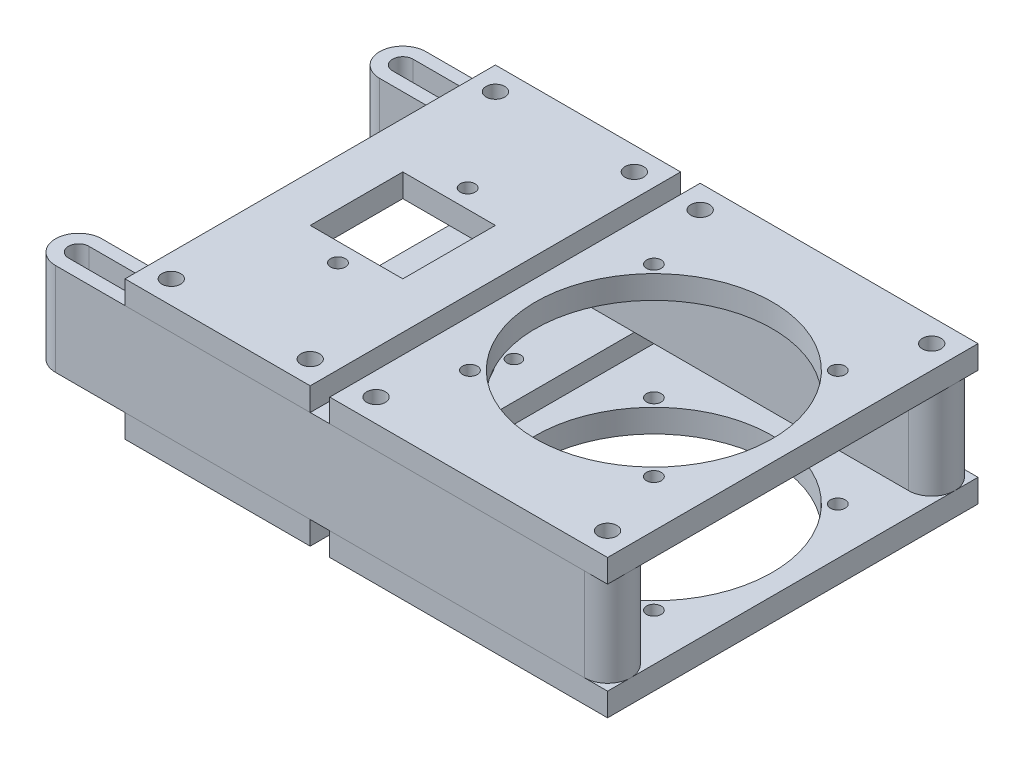
SolidWorks part; units mm, degrees
material "Alum Plate"
ref_plane "Front Plane" through (0, 0, 0) normal (0, 0, 1) x (1, 0, 0)
ref_plane "Top Plane" through (0, 0, 0) normal (0, 1, 0) x (1, 0, 0)
ref_plane "Right Plane" through (0, 0, 0) normal (1, 0, 0) x (0, 0, -1)
sketch "Sketch2" plane through (0, 0, 0) normal (0, 1, 0) x (1, 0, 0)
  line L0 (0, 0) -> (-68.8619, 0) construction
  line L1 (-38.1, -50.8) -> (-38.1, 50.8)
  line L2 (-38.1, 50.8) -> (38.1, 50.8)
  line L4 (-38.1, -50.8) -> (38.1, -50.8)
  line L5 (38.1, 50.8) -> (38.1, -50.8)
  line L7 (-94.2619, 50.8) -> (-43.4619, 50.8)
  line L8 (-81.5619, 12.7) -> (-56.1619, 12.7) construction
  line L9 (-81.5619, 12.7) -> (-81.5619, -12.7) construction
  line L10 (-81.5619, -12.7) -> (-56.1619, -12.7) construction
  line L11 (-56.1619, 12.7) -> (-56.1619, -12.7) construction
  line L12 (-81.5619, 12.7) -> (-56.1619, -12.7) construction
  line L13 (-81.5619, -12.7) -> (-56.1619, 12.7) construction
  line L14 (-38.1, -50.8) -> (38.1, 50.8) construction
  line L15 (-94.2619, 50.8) -> (-94.2619, -50.8)
  line L16 (-94.2619, -50.8) -> (-43.4619, -50.8)
  line L17 (-43.4619, 50.8) -> (-43.4619, -50.8)
  line L18 (-94.2619, 50.8) -> (-43.4619, -50.8) construction
  line L19 (-94.2619, -50.8) -> (-43.4619, 50.8) construction
  circle A0 centre (0, 0) radius 32.5
  circle A1 centre (-68.8619, 0) radius 18 construction
  point P5 (-34.431, 0)
  point P8 (-38.1, 0)
  dimension "D1" = 65
  dimension "D2" = 36
  dimension "D3" = 68.8619
  dimension "D4" = 38.1
  dimension "D5" = 50.8
  dimension "D6" = 25.4
  dimension "D7" = 25.4
  dimension "D8" = 50.8
extrude "Boss-Extrude1" add sketch "Sketch2" against normal blind 6.35 from offset 19.05
mirror "Mirror1" about plane through (0, 0, 0) normal (0, 1, 0) of bodies 101 109
sketch "Sketch3" plane through (0, 19.05, 0) normal (0, 1, 0) x (1, 0, 0)
  line L1 (-81.5619, -12.7) -> (-56.1619, -12.7)
  line L2 (-81.5619, -12.7) -> (-81.5619, 12.7)
  line L3 (-81.5619, 12.7) -> (-56.1619, 12.7)
  line L4 (-56.1619, -12.7) -> (-56.1619, 12.7)
  line L5 (-81.5619, -12.7) -> (-56.1619, 12.7) construction
  line L6 (-81.5619, 12.7) -> (-56.1619, -12.7) construction
  point P4 (-68.8619, 0)
extrude "Cut-Extrude1" cut sketch "Sketch3" against normal up to next (6.35 mm away)
sketch "Sketch4" plane through (0, -19.05, 0) normal (0, -1, 0) x (1, 0, 0)
  circle A0 centre (-68.8619, 0) radius 18 construction
  circle A1 centre (-68.8619, 0) radius 18
extrude "Cut-Extrude2" cut sketch "Sketch4" against normal up to next (6.35 mm away)
sketch "Sketch5" plane through (0, -19.05, 0) normal (0, -1, 0) x (1, 0, 0)
  line L1 (-84.1019, 15.24) -> (-53.6219, 15.24) construction
  line L2 (-84.1019, 15.24) -> (-84.1019, -15.24) construction
  line L3 (-84.1019, -15.24) -> (-53.6219, -15.24) construction
  line L4 (-53.6219, 15.24) -> (-53.6219, -15.24) construction
  line L5 (-84.1019, 15.24) -> (-53.6219, -15.24) construction
  line L6 (-84.1019, -15.24) -> (-53.6219, 15.24) construction
  circle A0 centre (-84.1019, 15.24) radius 1.905
  circle A1 centre (-53.6219, 15.24) radius 1.905
  circle A2 centre (-53.6219, -15.24) radius 1.905
  circle A3 centre (-84.1019, -15.24) radius 1.905
  point P0 (-68.8619, 0)
  dimension "D2" = 3.81
  dimension "D1" = 30.48
extrude "Cut-Extrude3" cut sketch "Sketch5" against normal up to next (6.35 mm away)
sketch "Sketch6" plane through (0, 19.05, 0) normal (0, 1, 0) x (1, 0, 0)
  line L0 (-38.1, -44.45) -> (-31.75, -44.45) construction
  line L2 (-31.75, -44.45) -> (-31.75, -50.8) construction
  line L3 (-38.1, -50.8) -> (38.1, -50.8) construction
  line L4 (-38.1, 44.45) -> (-31.75, 44.45) construction
  line L5 (-31.75, 44.45) -> (-31.75, 50.8) construction
  line L6 (38.1, 50.8) -> (-38.1, 50.8) construction
  line L7 (38.1, 44.45) -> (31.75, 44.45) construction
  line L8 (38.1, -50.8) -> (38.1, 50.8) construction
  line L9 (31.75, 44.45) -> (31.75, 50.8) construction
  line L10 (31.75, -50.8) -> (31.75, -44.45) construction
  line L11 (31.75, -44.45) -> (38.1, -44.45) construction
  line L12 (-38.1, 50.8) -> (-38.1, -50.8) construction
  line L13 (25.226, 25.226) -> (-25.226, 25.226) construction
  line L14 (25.226, 25.226) -> (25.226, -25.226) construction
  line L15 (25.226, -25.226) -> (-25.226, -25.226) construction
  line L16 (-25.226, 25.226) -> (-25.226, -25.226) construction
  line L17 (25.226, 25.226) -> (-25.226, -25.226) construction
  line L18 (25.226, -25.226) -> (-25.226, 25.226) construction
  line L19 (-49.8119, -50.8) -> (-49.8119, -44.45) construction
  line L20 (-94.2619, -50.8) -> (-43.4619, -50.8) construction
  line L21 (-49.8119, -44.45) -> (-43.4619, -44.45) construction
  line L22 (-43.4619, -50.8) -> (-43.4619, 50.8) construction
  line L23 (-68.8619, -50.8) -> (-68.8619, 50.8) construction
  line L24 (-43.4619, 50.8) -> (-94.2619, 50.8) construction
  line L25 (-94.2619, 0) -> (-43.4619, 0) construction
  line L26 (-94.2619, 50.8) -> (-94.2619, -50.8) construction
  circle A0 centre (-31.75, 44.45) radius 2.5527
  circle A1 centre (31.75, 44.45) radius 2.5527
  circle A2 centre (31.75, -44.45) radius 2.5527
  circle A3 centre (-31.75, -44.45) radius 2.5527
  circle A4 centre (-25.226, 25.226) radius 2.0193
  circle A5 centre (25.226, 25.226) radius 2.0193
  circle A6 centre (25.226, -25.226) radius 2.0193
  circle A7 centre (-25.226, -25.226) radius 2.0193
  circle A8 centre (0, 0) radius 32.5 construction
  circle A9 centre (-49.8119, -44.45) radius 2.5527
  circle A10 centre (-49.8119, 44.45) radius 2.5527
  circle A11 centre (-87.9119, -44.45) radius 2.5527
  circle A12 centre (-87.9119, 44.45) radius 2.5527
  point P24 (0, 0)
  point P34 (-22.981, 22.981)
  dimension "D2" = 5.1054
  dimension "D3" = 4.0386
  dimension "D1" = 6.35
  dimension "D4" = 3.175
extrude "Cut-Extrude4" cut sketch "Sketch6" against normal through all
sketch "Sketch7" plane through (0, 19.05, 0) normal (0, 1, 0) x (1, 0, 0)
  line L0 (-68.8619, 12.7) -> (-68.8619, 17.78) construction
  line L2 (-68.8619, -12.7) -> (-68.8619, -17.78) construction
  line L4 (-56.1619, 12.7) -> (-81.5619, 12.7) construction
  line L5 (-81.5619, -12.7) -> (-56.1619, -12.7) construction
  circle A0 centre (-68.8619, 17.78) radius 2.0193
  circle A1 centre (-68.8619, -17.78) radius 2.0193
  dimension "D1" = 4.0386
  dimension "D2" = 5.08
extrude "Cut-Extrude5" cut sketch "Sketch7" against normal up to next (6.35 mm away)
sketch "Sketch8" plane through (0, -12.7, 0) normal (0, 1, 0) x (1, 0, 0)
  line L0 (31.75, -44.45) -> (-113.3119, -44.45) construction
  line L1 (31.75, -50.8) -> (-113.3119, -50.8)
  line L2 (31.75, -38.1) -> (-113.3119, -38.1)
  line L3 (-94.2619, -50.8) -> (-43.4619, -50.8) construction
  line L4 (31.75, 44.45) -> (-113.3119, 44.45) construction
  line L5 (31.75, 38.1) -> (-113.3119, 38.1)
  line L6 (31.75, 50.8) -> (-113.3119, 50.8)
  line L7 (-43.4619, 50.8) -> (-94.2619, 50.8) construction
  line L8 (-113.3119, -44.45) -> (-113.3119, 44.45) construction
  line L9 (-49.8119, 44.45) -> (-113.3119, 44.45) construction
  line L10 (-49.8119, 41.656) -> (-113.3119, 41.656)
  line L11 (-49.8119, 47.244) -> (-113.3119, 47.244)
  line L12 (-49.8119, -44.45) -> (-113.3119, -44.45) construction
  line L13 (-49.8119, -47.244) -> (-113.3119, -47.244)
  line L14 (-49.8119, -41.656) -> (-113.3119, -41.656)
  arc A0 (31.75, -50.8) -> (31.75, -38.1) centre (31.75, -44.45) ccw
  arc A1 (-113.3119, -38.1) -> (-113.3119, -50.8) centre (-113.3119, -44.45) ccw
  arc A2 (31.75, 38.1) -> (31.75, 50.8) centre (31.75, 44.45) ccw
  arc A3 (-113.3119, 50.8) -> (-113.3119, 38.1) centre (-113.3119, 44.45) ccw
  arc A6 (-49.8119, 41.656) -> (-49.8119, 47.244) centre (-49.8119, 44.45) ccw
  arc A7 (-113.3119, 47.244) -> (-113.3119, 41.656) centre (-113.3119, 44.45) ccw
  arc A8 (-49.8119, -47.244) -> (-49.8119, -41.656) centre (-49.8119, -44.45) ccw
  arc A9 (-113.3119, -41.656) -> (-113.3119, -47.244) centre (-113.3119, -44.45) ccw
  point P3 (-40.781, -44.45)
  point P13 (-40.781, 44.45)
  point P23 (-87.9119, 44.45)
  point P24 (-81.5619, 44.45)
  point P32 (-81.5619, -44.45)
  dimension "D1" = 25.4
  dimension "D2" = 5.588
extrude "Boss-Extrude2" add sketch "Sketch8" along normal up to surface (25.4 mm away) separate body up to face at (-68.8619, 12.7, -15.7607)
